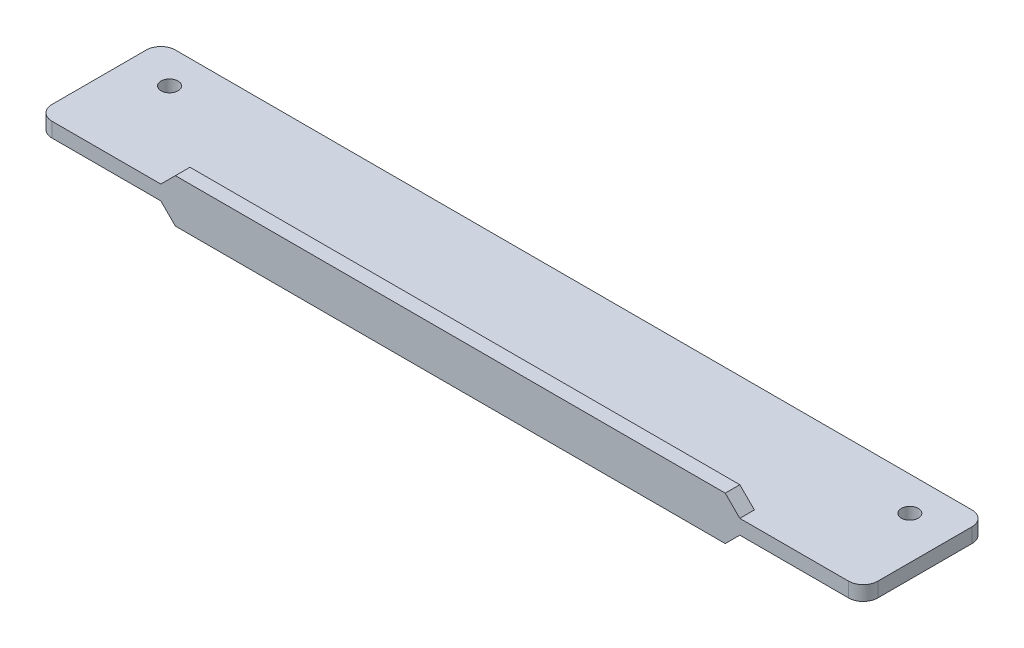
SolidWorks part; units mm, degrees
ref_plane "Front Plane" through (0, 0, 0) normal (0, 0, 1) x (1, 0, 0)
ref_plane "Top Plane" through (0, 0, 0) normal (0, 1, 0) x (1, 0, 0)
ref_plane "Right Plane" through (0, 0, 0) normal (1, 0, 0) x (0, 0, -1)
sketch "Sketch1" plane through (0, 0, 0) normal (0, 1, 0) x (1, 0, 0)
  line L1 (-74.9462, 20.7168) -> (95.0538, 20.7168)
  line L2 (-74.9462, 20.7168) -> (-74.9462, -4.6832)
  line L3 (-74.9462, -4.6832) -> (95.0538, -4.6832)
  line L4 (95.0538, 20.7168) -> (95.0538, -4.6832)
  dimension "D1" = 170
  dimension "D2" = 25.4
extrude "Boss-Extrude1" add sketch "Sketch1" along normal blind 3
fillet "Fillet1" radius 3 4 edges at (95.0538, 1.5, -20.7168) (95.0538, 1.5, 4.6832) (-74.9462, 1.5, -20.7168) (-74.9462, 1.5, 4.6832)
sketch "Sketch2" plane through (0, 3, 0) normal (0, 1, 0) x (1, 0, 0)
  line L0 (95.0538, -1.6832) -> (95.0538, 17.7168) construction
  line L1 (92.0538, 20.7168) -> (-71.9462, 20.7168) construction
  circle A0 centre (86.2538, 13.7168) radius 1.75
  circle A1 centre (-66.1462, 13.7168) radius 1.75
  dimension "D1" = 3.5
  dimension "D2" = 3.5
  dimension "D3" = 152.4
  dimension "D4" = 8.8
  dimension "D5" = 7
extrude "Cut-Extrude1" cut sketch "Sketch2" against normal blind 3
sketch "Sketch3" plane through (0, 0, 4.6832) normal (0, 0, 1) x (1, 0, 0)
  line L0 (-71.9462, 3) -> (92.0538, 3) construction
  line L1 (-49.5462, 6) -> (69.6538, 6)
  line L2 (-49.5462, 6) -> (-49.5462, -3)
  line L3 (-49.5462, -3) -> (69.6538, -3)
  line L4 (69.6538, 6) -> (69.6538, -3)
  line L5 (-71.9462, 0) -> (92.0538, 0) construction
  line L6 (-74.9462, 0) -> (-74.9462, 3) construction
  line L7 (95.0538, 3) -> (95.0538, 0) construction
  dimension "D1" = 3
  dimension "D2" = 3
  dimension "D3" = 25.4
  dimension "D4" = 25.4
extrude "Boss-Extrude2" add sketch "Sketch3" against normal blind 3
chamfer "Chamfer1" distance 3 angle 45 4 edges at (-49.5462, -3, 3.1832) (69.6538, -3, 3.1832) (69.6538, 6, 3.1832) (-49.5462, 6, 3.1832)
